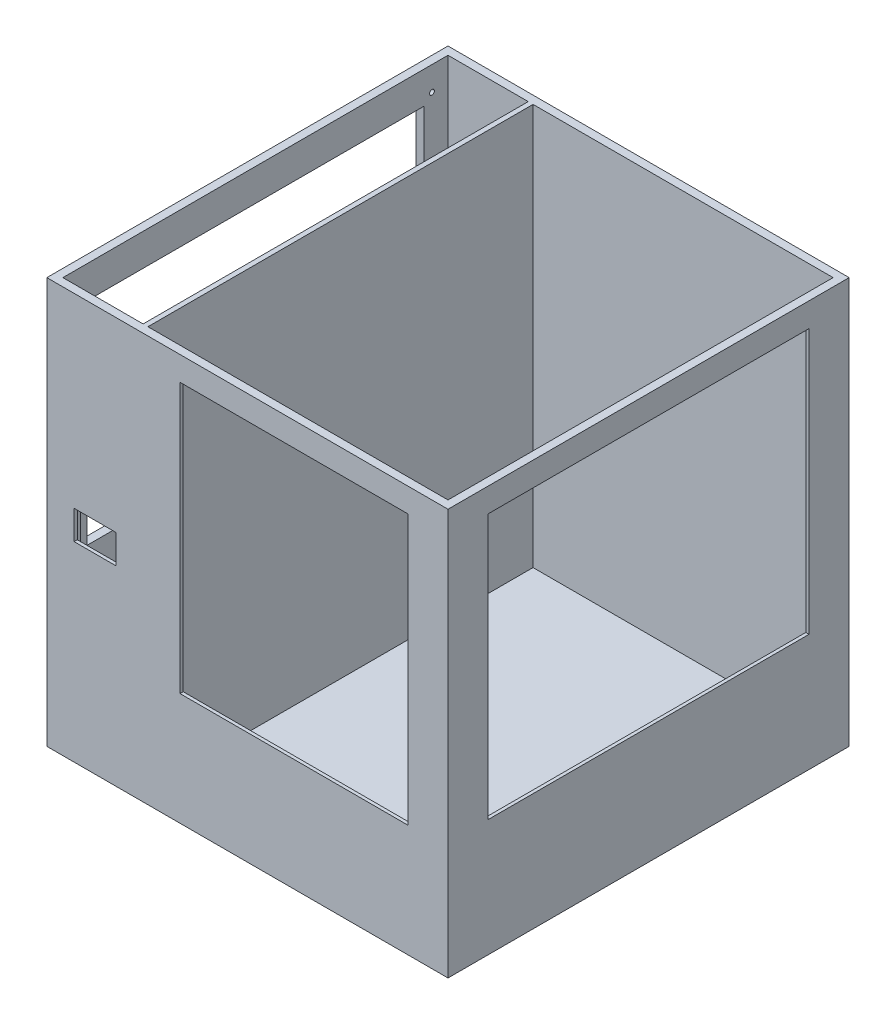
SolidWorks part; units mm, degrees
ref_plane "Спереди" through (0, 0, 0) normal (0, 0, 1) x (1, 0, 0)
ref_plane "Сверху" through (0, 0, 0) normal (0, 1, 0) x (1, 0, 0)
ref_plane "Справа" through (0, 0, 0) normal (1, 0, 0) x (0, 0, -1)
sketch "Эскиз1" plane through (0, 0, 0) normal (0, 1, 0) x (1, 0, 0)
  line L1 (-125, -125) -> (125, -125)
  line L2 (-125, -125) -> (-125, 125)
  line L3 (-125, 125) -> (125, 125)
  line L4 (125, -125) -> (125, 125)
  line L5 (-125, -125) -> (125, 125) construction
  line L6 (-125, 125) -> (125, -125) construction
  point P0 (0, 0)
  dimension "D1" = 250
  dimension "D2" = 250
extrude "Бобышка-Вытянуть1" add sketch "Эскиз1" along normal blind 3
sketch "Эскиз2" plane through (0, 3, 0) normal (0, 1, 0) x (1, 0, 0)
  line L1 (-125, -125) -> (125, -125)
  line L2 (-125, -125) -> (-125, 125)
  line L3 (-125, 125) -> (125, 125)
  line L4 (125, -125) -> (125, 125)
  line L5 (-125, -125) -> (125, 125) construction
  line L6 (-125, 125) -> (125, -125) construction
  line L7 (-120, -120) -> (120, -120)
  line L8 (-120, -120) -> (-120, 120)
  line L9 (-120, 120) -> (120, 120)
  line L10 (120, -120) -> (120, 120)
  line L11 (-120, -120) -> (120, 120) construction
  line L12 (-120, 120) -> (120, -120) construction
  point P0 (0, 0)
  point P6 (0, 0)
  dimension "D1" = 250
  dimension "D2" = 250
  dimension "D3" = 240
  dimension "D4" = 240
extrude "Бобышка-Вытянуть2" add sketch "Эскиз2" along normal blind 250
sketch "Эскиз3" plane through (0, 3, 0) normal (0, 1, 0) x (1, 0, 0)
  line L0 (120, 120) -> (-120, 120) construction
  line L1 (-70, 120) -> (-67, 120)
  line L2 (-70, 120) -> (-70, -120)
  line L3 (-70, -120) -> (-67, -120)
  line L4 (-67, 120) -> (-67, -120)
  line L5 (-120, -120) -> (120, -120) construction
  line L6 (-120, 120) -> (-120, -120) construction
  dimension "D1" = 3
  dimension "D2" = 50
extrude "Бобышка-Вытянуть3" add sketch "Эскиз3" along normal blind 250
sketch "Эскиз8" plane through (125, 0, 0) normal (1, 0, 0) x (0, 0, -1)
  line L0 (-125, 3) -> (125, 3) construction
  line L1 (-100, 73) -> (100, 73)
  line L2 (-100, 73) -> (-100, 238)
  line L3 (-100, 238) -> (100, 238)
  line L4 (100, 73) -> (100, 238)
  line L5 (-100, 73) -> (100, 238) construction
  line L6 (-100, 238) -> (100, 73) construction
  line L7 (-125, 253) -> (125, 253) construction
  line L8 (125, 253) -> (125, 0) construction
  point P0 (0, 155.5)
  dimension "D1" = 70
  dimension "D2" = 15
  dimension "D3" = 25
extrude "Вырез-Вытянуть4" cut sketch "Эскиз8" against normal blind 8
sketch "Эскиз9" plane through (120, 0, 0) normal (-1, 0, 0) x (0, 0, 1)
  line L0 (100, 73) -> (100, 238) construction
  line L1 (-110, 63) -> (110, 63)
  line L2 (-110, 63) -> (-110, 248)
  line L3 (-110, 248) -> (110, 248)
  line L4 (110, 63) -> (110, 248)
  line L5 (-110, 63) -> (110, 248) construction
  line L6 (-110, 248) -> (110, 63) construction
  line L7 (100, 238) -> (-100, 238) construction
  point P0 (0, 155.5)
  dimension "D1" = 10
  dimension "D2" = 10
extrude "Вырез-Вытянуть5" cut sketch "Эскиз9" against normal blind 3
sketch "Эскиз11" plane through (0, 0, 125) normal (0, 0, 1) x (1, 0, 0)
  line L0 (125, 253) -> (125, 0) construction
  line L1 (-42, 238) -> (100, 238)
  line L2 (-42, 238) -> (-42, 70)
  line L3 (-42, 70) -> (100, 70)
  line L4 (100, 238) -> (100, 70)
  line L5 (-125, 0) -> (125, 0) construction
  line L6 (-125, 253) -> (125, 253) construction
  line L7 (-125, 253) -> (-125, 0) construction
  dimension "D1" = 25
  dimension "D2" = 70
  dimension "D3" = 15
  dimension "D4" = 83
extrude "Вырез-Вытянуть6" cut sketch "Эскиз11" against normal blind 10
sketch "Эскиз12" plane through (0, 0, 120) normal (0, 0, -1) x (-1, 0, 0)
  line L0 (42, 238) -> (-100, 238) construction
  line L1 (-110, 248) -> (52, 248)
  line L2 (-110, 248) -> (-110, 60)
  line L3 (-110, 60) -> (52, 60)
  line L4 (52, 248) -> (52, 60)
  line L5 (42, 238) -> (42, 70) construction
  line L6 (-100, 238) -> (-100, 70) construction
  line L7 (42, 70) -> (-100, 70) construction
  dimension "D1" = 10
  dimension "D2" = 10
  dimension "D3" = 10
  dimension "D4" = 10
extrude "Вырез-Вытянуть7" cut sketch "Эскиз12" against normal blind 3
sketch "Эскиз16" plane through (0, 0, 125) normal (0, 0, 1) x (1, 0, 0)
  line L0 (-125, 253) -> (-125, 0) construction
  line L1 (-108, 119) -> (-82, 119)
  line L2 (-108, 119) -> (-108, 137)
  line L3 (-108, 137) -> (-82, 137)
  line L4 (-82, 119) -> (-82, 137)
  line L5 (-108, 119) -> (-82, 137) construction
  line L6 (-108, 137) -> (-82, 119) construction
  line L8 (-125, 0) -> (125, 0) construction
  point P0 (-95, 128)
  dimension "D1" = 26
  dimension "D2" = 18
  dimension "D3" = 30
  dimension "D4" = 128
extrude "Вырез-Вытянуть10" cut sketch "Эскиз16" against normal blind 5
sketch "Эскиз17" plane through (-125, 0, 0) normal (-1, 0, 0) x (0, 0, 1)
  line L0 (-125, 0) -> (125, 0) construction
  line L1 (101, 86) -> (110, 86)
  line L2 (101, 86) -> (101, 75)
  line L3 (101, 75) -> (110, 75)
  line L4 (110, 86) -> (110, 75)
  line L5 (66, 83) -> (81, 83)
  line L6 (66, 83) -> (66, 75)
  line L7 (66, 75) -> (81, 75)
  line L8 (81, 83) -> (81, 75)
  line L9 (125, 253) -> (125, 0) construction
  dimension "D1" = 11
  dimension "D2" = 9
  dimension "D3" = 8
  dimension "D4" = 15
  dimension "D5" = 75
  dimension "D6" = 75
  dimension "D7" = 20
  dimension "D8" = 15
extrude "Вырез-Вытянуть11" cut sketch "Эскиз17" against normal blind 10
sketch "Эскиз21" plane through (0, 0, 120) normal (0, 0, -1) x (-1, 0, 0)
  line L1 (81, 114) -> (109, 114)
  line L2 (81, 114) -> (81, 142)
  line L3 (81, 142) -> (109, 142)
  line L4 (109, 114) -> (109, 142)
  line L5 (81, 114) -> (109, 142) construction
  line L6 (81, 142) -> (109, 114) construction
  point P0 (95, 128)
  dimension "D1" = 28
  dimension "D2" = 28
extrude "Вырез-Вытянуть14" cut sketch "Эскиз21" against normal blind 3
sketch "Эскиз22" plane through (0, 0, -120) normal (0, 0, 1) x (1, 0, 0)
  line L0 (-120, 253) -> (-120, 3) construction
  line L5 (-120, 73) -> (-70, 73)
  line L6 (-120, 73) -> (-120, 70)
  line L7 (-120, 70) -> (-70, 70)
  line L8 (-70, 73) -> (-70, 70)
  line L9 (-70, 253) -> (-70, 3) construction
  line L10 (-70, 3) -> (-120, 3) construction
  dimension "D1" = 3
  dimension "D2" = 67
extrude "Бобышка-Вытянуть4" add sketch "Эскиз22" along normal blind 240
sketch "Эскиз24" plane through (-67, 0, 0) normal (1, 0, 0) x (0, 0, -1)
  line L0 (-120, 3) -> (120, 3) construction
  line L1 (120, 253) -> (120, 3) construction
  circle A0 centre (86.5, 53) radius 4
  dimension "D1" = 8
  dimension "D2" = 50
  dimension "D3" = 33.5
extrude "Вырез-Вытянуть15" cut sketch "Эскиз24" against normal blind 10
sketch "Эскиз25" plane through (-125, 0, 0) normal (-1, 0, 0) x (0, 0, 1)
  line L0 (-125, 253) -> (125, 253) construction
  line L1 (-105, 233) -> (105, 233)
  line L2 (-105, 233) -> (-105, 101)
  line L3 (-105, 101) -> (105, 101)
  line L4 (105, 233) -> (105, 101)
  line L5 (125, 253) -> (125, 0) construction
  line L6 (-125, 253) -> (-125, 0) construction
  line L7 (110, 86) -> (101, 86) construction
  dimension "D1" = 20
  dimension "D2" = 20
  dimension "D3" = 20
  dimension "D4" = 15
extrude "Вырез-Вытянуть16" cut sketch "Эскиз25" against normal blind 10
sketch "Эскиз26" plane through (-125, 0, 0) normal (-1, 0, 0) x (0, 0, 1)
  line L0 (-105, 101) -> (105, 101) construction
  line L1 (-105, 233) -> (-105, 101) construction
  line L2 (105, 101) -> (105, 233) construction
  line L3 (105, 233) -> (-105, 233) construction
  circle A0 centre (-110, 238) radius 1.5
  circle A1 centre (110, 238) radius 1.5
  circle A2 centre (110, 96) radius 1.5
  circle A3 centre (-110, 96) radius 1.5
  dimension "D1" = 3
  dimension "D2" = 3
  dimension "D3" = 3
  dimension "D4" = 3
  dimension "D5" = 5
  dimension "D6" = 5
  dimension "D7" = 5
  dimension "D8" = 5
  dimension "D9" = 5
  dimension "D10" = 5
  dimension "D11" = 5
  dimension "D12" = 5
extrude "Вырез-Вытянуть17" cut sketch "Эскиз26" against normal blind 10
